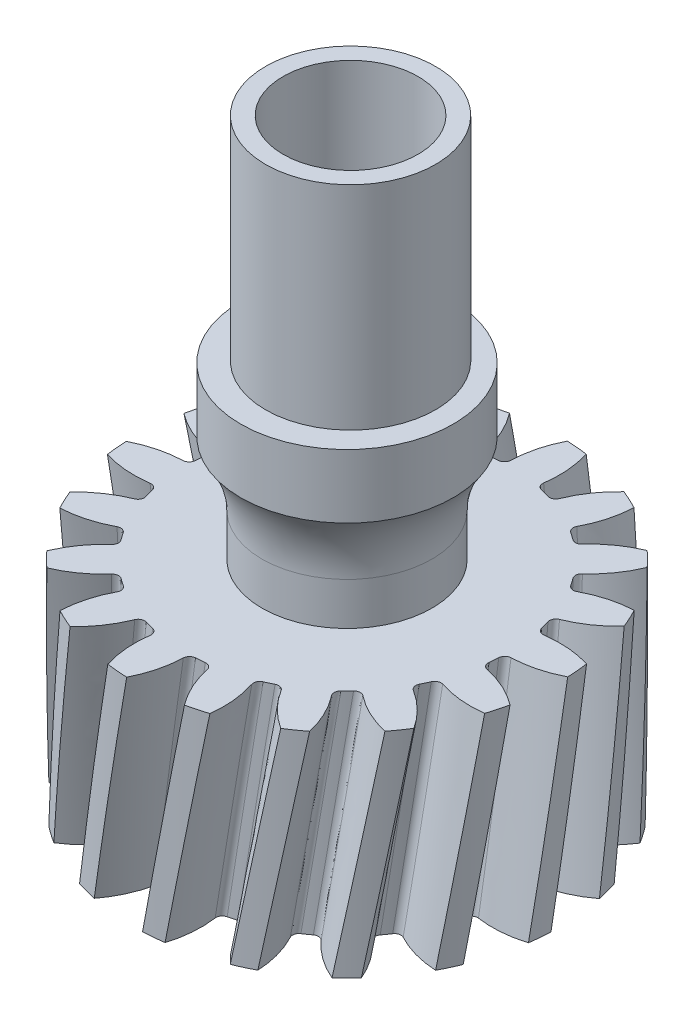
SolidWorks part; units mm, degrees
ref_plane "Front Plane" through (0, 0, 0) normal (0, 0, 1) x (1, 0, 0)
ref_plane "Top Plane" through (0, 0, 0) normal (0, 1, 0) x (1, 0, 0)
ref_plane "Right Plane" through (0, 0, 0) normal (1, 0, 0) x (0, 0, -1)
sketch "Sketch1" plane through (0, 0, 0) normal (0, 1, 0) x (1, 0, 0)
  circle A0 centre (0, 0) radius 9
  circle A1 centre (0, 0) radius 10
  circle A2 centre (0, 0) radius 7.6
  dimension "D1" = 18
  dimension "D2" = 20
  dimension "D3" = 2.4
extrude "Boss-Extrude1" add sketch "Sketch1" along normal mid plane 10 contours A1
sketch "Sketch2" plane through (0, 0, 0) normal (0, 1, 0) x (1, 0, 0)
  line L0 (0, 0) -> (0, 10) construction
  line L1 (-0.7844, 8.9658) -> (0.7844, 8.9658) construction
  line L2 (-0.4941, 7.5839) -> (0, 0) construction
  line L3 (-1.488, 10.8989) -> (0, 6.8106) construction
  line L4 (0, 0) -> (1.7365, 9.8481) construction
  line L5 (0.7844, 8.9658) -> (2.3294, 8.6933) construction
  circle A0 centre (0, 0) radius 10 construction
  arc A1 (-1.9786, 10.8206) -> (-0.4941, 7.5839) centre (-5.472, 7.2596) cw
  arc A2 (1.9786, 10.8206) -> (0.4941, 7.5839) centre (5.472, 7.2596) ccw
  circle A3 centre (0, 0) radius 7.6 construction
  arc A4 (0.4941, 7.5839) -> (-0.4941, 7.5839) centre (0, 0) ccw
  circle A5 centre (0, 0) radius 9 construction
  circle A7 centre (0, 0) radius 11
  arc A8 (1.9786, 10.8206) -> (-1.9786, 10.8206) centre (0, 0) ccw
  circle A9 centre (0, 0) radius 10 construction
  dimension "D2" = 20
  dimension "D3" = 10
sketch "Sketch5" plane through (0, 0, 0) normal (0, 0, 1) x (1, 0, 0)
  line L0 (0.8816, -5) -> (-0.8816, 5)
  line L1 (-10, -5) -> (10, -5) construction
  line L2 (10, 5) -> (-10, 5) construction
  line L3 (0, -5) -> (0, 5) construction
  dimension "D1" = 10
curve "Curve1"
sketch "Sketch6" plane through (0, 5, 0) normal (0, 1, 0) x (0.9961, 0, -0.0882)
  line L0 (0, 0) -> (0, 10) construction
  line L1 (-0.7844, 8.9658) -> (0.7844, 8.9658) construction
  line L2 (-0.4941, 7.5839) -> (0, 0) construction
  line L3 (-1.488, 10.8989) -> (0, 6.8106) construction
  line L4 (0, 0) -> (1.7365, 9.8481) construction
  line L5 (0.7844, 8.9658) -> (2.3294, 8.6933) construction
  arc A1 (-1.9786, 10.8206) -> (-0.4941, 7.5839) centre (-5.472, 7.2596) cw
  arc A2 (1.9786, 10.8206) -> (0.4941, 7.5839) centre (5.472, 7.2596) ccw
  arc A4 (0.4941, 7.5839) -> (-0.4941, 7.5839) centre (0, 0) ccw
  arc A8 (1.9786, 10.8206) -> (-1.9786, 10.8206) centre (0, 0) ccw
sketch "Sketch7" plane through (0, -5, 0) normal (0, 1, 0) x (0.9961, 0, 0.0882)
  line L0 (0, 0) -> (0, 10) construction
  line L1 (-0.7844, 8.9658) -> (0.7844, 8.9658) construction
  line L2 (-0.4941, 7.5839) -> (0, 0) construction
  line L3 (-1.488, 10.8989) -> (0, 6.8106) construction
  line L4 (0, 0) -> (1.7365, 9.8481) construction
  line L5 (0.7844, 8.9658) -> (2.3294, 8.6933) construction
  arc A1 (-1.9786, 10.8206) -> (-0.4941, 7.5839) centre (-5.472, 7.2596) cw
  arc A2 (1.9786, 10.8206) -> (0.4941, 7.5839) centre (5.472, 7.2596) ccw
  arc A4 (0.4941, 7.5839) -> (-0.4941, 7.5839) centre (0, 0) ccw
  arc A8 (1.9786, 10.8206) -> (-1.9786, 10.8206) centre (0, 0) ccw
loft "Cut-Loft1" cut profiles "Sketch6", "Sketch2", "Sketch7" start constraint default end constraint default
fillet "Fillet2" radius 0.3 2 edges
pattern_circular "CirPattern3" count 18 over 360 about axis through (0, 5, 0) along (0, -1, 0) of "Cut-Loft1", "Fillet2"
sketch "Sketch8" plane through (0, 5, 0) normal (0, 1, 0) x (1, 0, 0)
  circle A0 centre (0, 0) radius 4
  dimension "D1" = 8
extrude "Boss-Extrude2" add sketch "Sketch8" along normal blind 5
sketch "Sketch9" plane through (0, 10, 0) normal (0, 1, 0) x (1, 0, 0)
  circle A0 centre (0, 0) radius 5
  dimension "D1" = 10
extrude "Boss-Extrude4" add sketch "Sketch9" along normal blind 3
fillet "Fillet3" radius 5 1 edges at (0, 10, 4)
sketch "Sketch10" plane through (0, 13, 0) normal (0, 1, 0) x (1, 0, 0)
  circle A0 centre (0, 0.1672) radius 4
  circle A1 centre (0, 0.1672) radius 3.175
  dimension "D1" = 8
  dimension "D2" = 6.35
extrude "Boss-Extrude5" add sketch "Sketch10" along normal blind 10
equation "\"module\"= 1"
equation "\"number of teeth\"= 18"
equation "\"D1@Sketch1\"=\"module\"*\"number of teeth\""
equation "\"D2@Sketch1\"=(\"number of teeth\"+2) * \"module\""
equation "\"D3@Sketch1\"=\"module\"*if( \"module\"=>1.25,2.25,2.4)"
equation "\"pressure angle\"= 20deg"
equation "\"D2@Sketch2\"=\"pressure angle\""
equation "\"D3@Sketch2\"=180 / \"number of teeth\""
equation "\"helix angle\"= - 10deg"
equation "\"D1@Fillet2\"=\"module\"*.3"
equation "\"D1@CirPattern3\"=\"number of teeth\""
